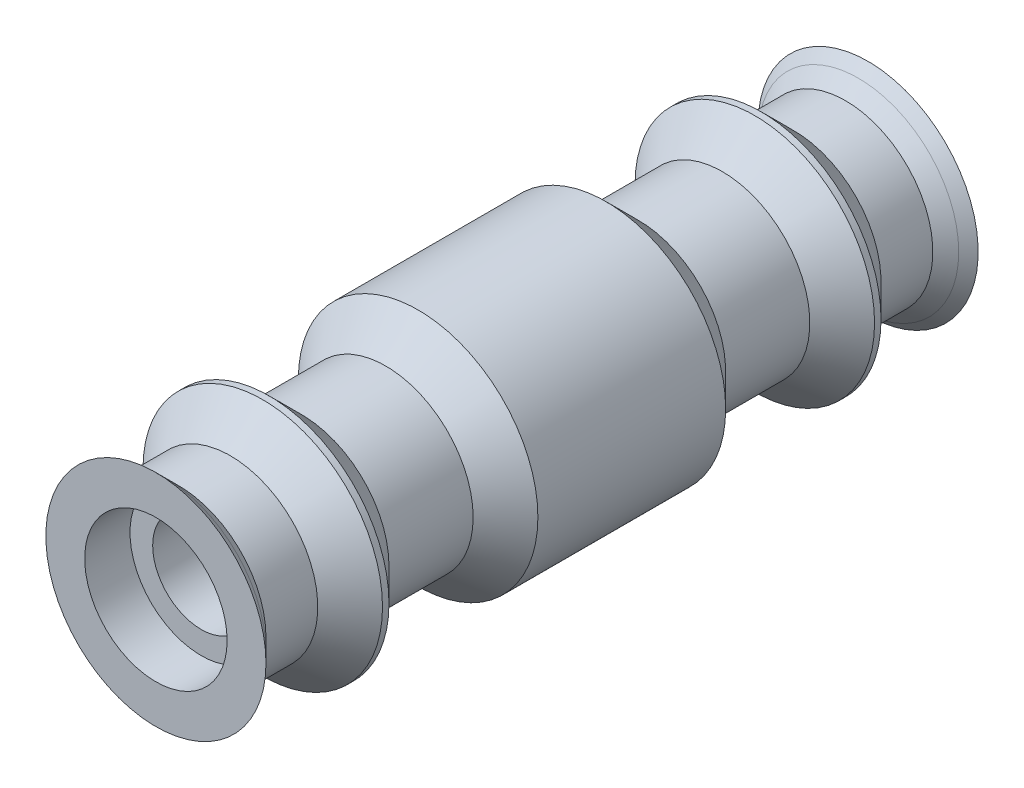
SolidWorks part; units mm, degrees
ref_plane "Front Plane" through (0, 0, 0) normal (0, 0, 1) x (1, 0, 0)
ref_plane "Top Plane" through (0, 0, 0) normal (0, 1, 0) x (1, 0, 0)
ref_plane "Right Plane" through (0, 0, 0) normal (1, 0, 0) x (0, 0, -1)
sketch "Sketch1" plane through (0, 0, 0) normal (0, 0, 1) x (1, 0, 0)
  circle A0 centre (0, 0) radius 11
  circle A1 centre (0, 0) radius 14
  circle A2 centre (0, 0) radius 5 construction
  dimension "D1" = 22
  dimension "D2" = 3
  dimension "D3" = 10
extrude "Boss-Extrude1" add sketch "Sketch1" along normal blind 105
sketch "Sketch2" plane through (0, 0, 105) normal (0, 0, 1) x (1, 0, 0)
  circle A0 centre (0, 0) radius 17.5
  circle A1 centre (0, 0) radius 11
  dimension "D1" = 35
  dimension "D2" = 22
extrude "Boss-Extrude2" add sketch "Sketch2" along normal blind 2
sketch "Sketch3" plane through (0, 0, 0) normal (0, 0, -1) x (-1, 0, 0)
  circle A0 centre (0, 0) radius 18.5
  circle A1 centre (0, 0) radius 11
  dimension "D1" = 22
  dimension "D2" = 37
extrude "Boss-Extrude3" add sketch "Sketch3" against normal blind 107
sketch "Sketch4" plane through (0, 0, 0) normal (0, 0, -1) x (-1, 0, 0)
  circle A0 centre (0, 0) radius 12
  circle A2 centre (0, 0) radius 18.5 construction
  dimension "D1" = 6.5
extrude "Boss-Extrude4" add sketch "Sketch4" against normal blind 107
sketch "Sketch5" plane through (0, 0, 0) normal (0, 0, -1) x (-1, 0, 0)
  circle A0 centre (0, 0) radius 11
  dimension "D1" = 22
extrude "Cut-Extrude1" cut sketch "Sketch5" against normal blind 5.5
sketch "Sketch6" plane through (0, 0, 107) normal (0, 0, 1) x (1, 0, 0)
  circle A0 centre (0, 0) radius 11
  dimension "D1" = 22
extrude "Cut-Extrude2" cut sketch "Sketch6" against normal blind 5.5
sketch "Sketch7" plane through (0, 0, 5.5) normal (0, 0, -1) x (-1, 0, 0)
  circle A0 centre (0, 0) radius 7.5
  dimension "D1" = 15
extrude "Cut-Extrude3" cut sketch "Sketch7" against normal blind 104
ref_plane "Plane1" through (0, 0, 53.5) normal (0, 0, -1) x (-1, 0, 0)
ref_plane "Plane2" through (0, 0, 2) normal (0, 0, -1) x (-1, 0, 0)
sketch "Sketch8" plane through (0, 0, 2) normal (0, 0, -1) x (-1, 0, 0)
  circle A0 centre (0, 0) radius 18.5
  circle A1 centre (0, 0) radius 13.5
  dimension "D1" = 27
  dimension "D2" = 5
ref_plane "Plane3" through (0, 0, 105) normal (0, 0, -1) x (-1, 0, 0)
sketch "Sketch9" plane through (0, 0, 105) normal (0, 0, -1) x (-1, 0, 0)
  circle A0 centre (0, 0) radius 13.5
  circle A1 centre (0, 0) radius 18.5
  dimension "D1" = 27
  dimension "D2" = 5
ref_plane "Plane4" through (0, 0, 21) normal (0, 0, -1) x (-1, 0, 0)
ref_plane "Plane6" through (0, 0, 86) normal (0, 0, -1) x (-1, 0, 0)
sketch "Sketch10" plane through (0, 0, 21) normal (0, 0, -1) x (-1, 0, 0)
  circle A0 centre (0, 0) radius 13.5
  circle A1 centre (0, 0) radius 18.5
  dimension "D1" = 27
  dimension "D2" = 5
extrude "Cut-Extrude9" cut sketch "Sketch9" along normal blind 8
extrude "Cut-Extrude10" cut sketch "Sketch10" against normal blind 13
extrude "Cut-Extrude11" cut sketch "Sketch8" against normal blind 8
sketch "Sketch13" plane through (0, 0, 86) normal (0, 0, -1) x (-1, 0, 0)
  circle A0 centre (0, 0) radius 13.5
  circle A1 centre (0, 0) radius 18.5
  dimension "D1" = 5
  dimension "D2" = 27
extrude "Cut-Extrude12" cut sketch "Sketch13" along normal blind 13
chamfer "Chamfer4" distance 5 angle 45 4 edges at (-18.5, 0, 2) (-18.5, 0, 10) (-18.5, 0, 105) (-18.5, 0, 97)
chamfer "Chamfer5" distance 5 angle 45 4 edges at (-18.5, 0, 34) (-18.5, 0, 73) (-18.5, 0, 86) (-18.5, 0, 21)
sketch "Sketch14" plane through (0, 0, 0) normal (0, 0, -1) x (-1, 0, 0)
  circle A0 centre (0, 0) radius 18.5
  circle A1 centre (0, 0) radius 18.5
  circle M1 centre (0, 0) radius 15.5
  circle M2 centre (0, 0) radius 11
  dimension "D1" = 37
extrude "Boss-Extrude5" add sketch "Sketch14" along normal blind 1.5 contours A0 M1 | M1 M2 region at (17.9767, 0, 0) region at (15.0616, 0, 0)
sketch "Sketch15" plane through (0, 0, 107) normal (0, 0, 1) x (1, 0, 0)
  circle A0 centre (0, 0) radius 18.5
  circle A1 centre (0, 0) radius 11
  dimension "D1" = 37
  dimension "D2" = 22
extrude "Boss-Extrude8" add sketch "Sketch15" along normal blind 1.5
chamfer "Chamfer7" distance 3 angle 45 2 edges at (18.5, 0, 107) (-18.5, 0, 0)
